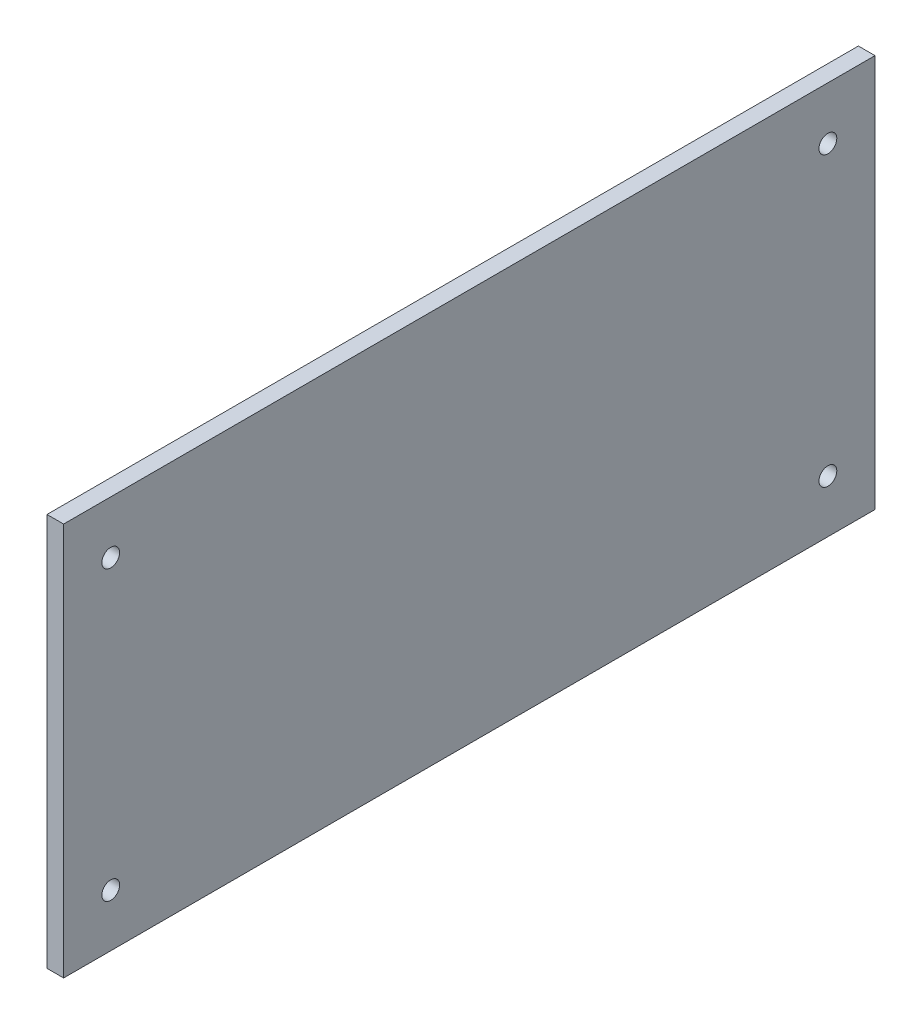
SolidWorks part; units mm, degrees
ref_plane "Front Plane" through (0, 0, 0) normal (0, 0, 1) x (1, 0, 0)
ref_plane "Top Plane" through (0, 0, 0) normal (0, 1, 0) x (1, 0, 0)
ref_plane "Right Plane" through (0, 0, 0) normal (1, 0, 0) x (0, 0, -1)
sketch "Sketch3" plane through (0, 0, 0) normal (1, 0, 0) x (0, 0, -1)
  line L0 (9, 10.05) -> (146, 10.05) construction
  line L1 (0, 0) -> (155, 0)
  line L2 (0, 0) -> (0, 75.1)
  line L3 (0, 75.1) -> (155, 75.1)
  line L4 (155, 0) -> (155, 75.1)
  line L5 (146, 10.05) -> (146, 65.05) construction
  line L6 (146, 65.05) -> (9, 65.05) construction
  line L7 (9, 65.05) -> (9, 10.05) construction
  circle A0 centre (9, 10.05) radius 1.7
  circle A1 centre (146, 10.05) radius 1.7
  circle A2 centre (146, 65.05) radius 1.7
  circle A3 centre (9, 65.05) radius 1.7
  dimension "D7" = 3.4
  dimension "D1" = 10.05
  dimension "D2" = 75.1
  dimension "D3" = 155
  dimension "D4" = 9
  dimension "D5" = 9
  dimension "D6" = 10.05
extrude "Boss-Extrude1" add sketch "Sketch3" along normal blind 3.175
